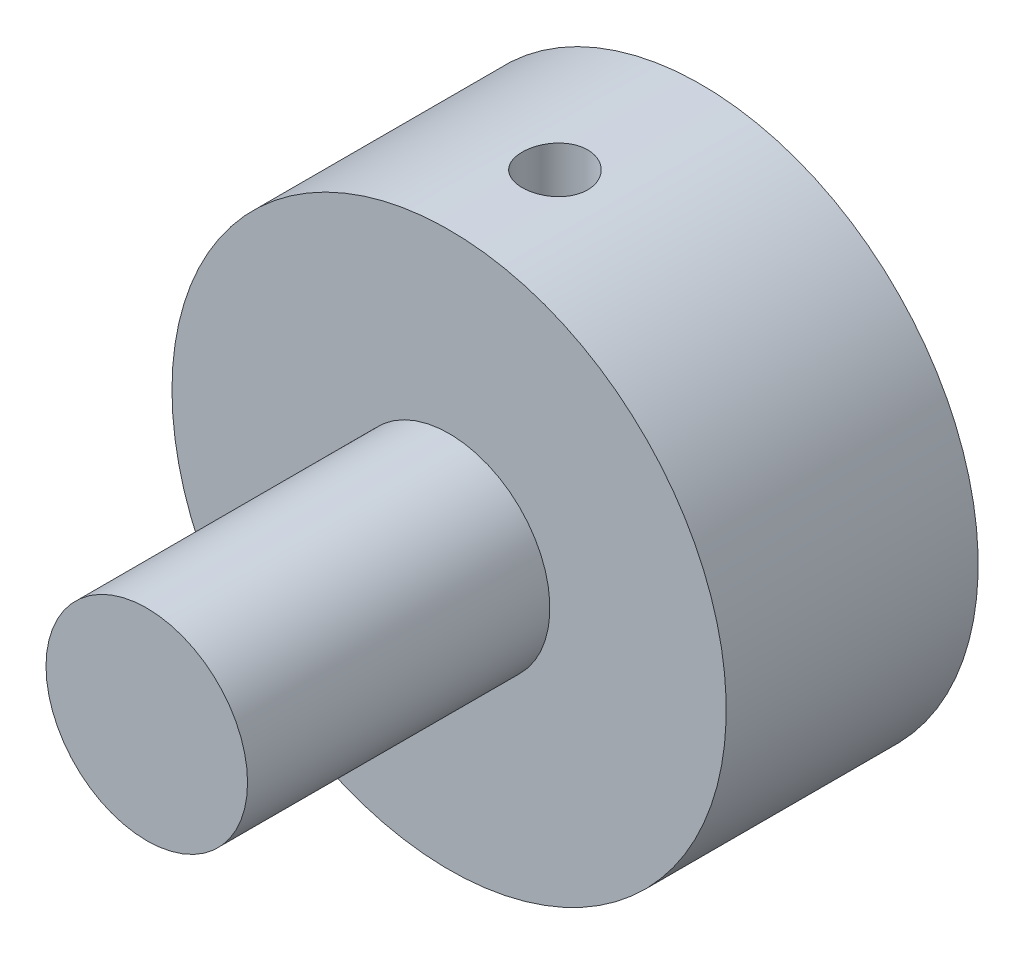
SolidWorks part; units mm, degrees
ref_plane "Front Plane" through (0, 0, 0) normal (0, 0, 1) x (1, 0, 0)
ref_plane "Top Plane" through (0, 0, 0) normal (0, 1, 0) x (1, 0, 0)
ref_plane "Right Plane" through (0, 0, 0) normal (1, 0, 0) x (0, 0, -1)
sketch "Sketch1" plane through (0, 0, 0) normal (0, 0, 1) x (1, 0, 0)
  circle A0 centre (0, 0) radius 4
  dimension "D1" = 8
extrude "Boss-Extrude1" add sketch "Sketch1" along normal blind 12
sketch "Sketch2" plane through (0, 0, 0) normal (0, 0, -1) x (-1, 0, 0)
  circle A0 centre (0, 0) radius 11
  dimension "D1" = 22
extrude "Boss-Extrude2" add sketch "Sketch2" along normal blind 10
sketch "Sketch3" plane through (0, 0, 0) normal (0, 1, 0) x (1, 0, 0)
  line L0 (-4, 0) -> (4, 0) construction
  circle A0 centre (0, 4.2) radius 1.3
  dimension "D1" = 2.6
  dimension "D2" = 4.2
extrude "Cut-Extrude1" cut sketch "Sketch3" against normal blind 20 and the other way blind 20
